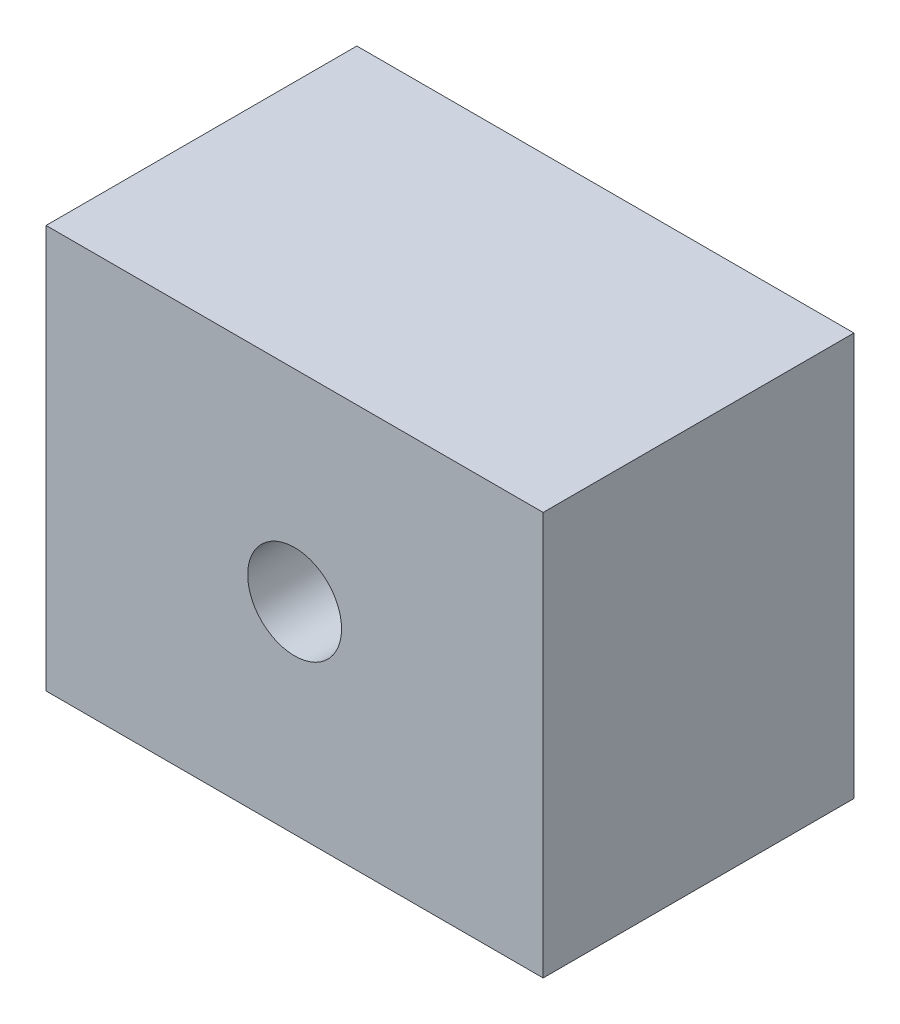
SolidWorks part; units mm, degrees
ref_plane "Front Plane" through (0, 0, 0) normal (0, 0, 1) x (1, 0, 0)
ref_plane "Top Plane" through (0, 0, 0) normal (0, 1, 0) x (1, 0, 0)
ref_plane "Right Plane" through (0, 0, 0) normal (1, 0, 0) x (0, 0, -1)
sketch "Sketch2" plane through (0, 0, 0) normal (0, 0, 1) x (1, 0, 0)
  line L1 (-67.2388, -54.5382) -> (67.2388, -54.5382)
  line L2 (-67.2388, -54.5382) -> (-67.2388, 54.5382)
  line L3 (-67.2388, 54.5382) -> (67.2388, 54.5382)
  line L4 (67.2388, -54.5382) -> (67.2388, 54.5382)
  line L5 (-67.2388, -54.5382) -> (67.2388, 54.5382) construction
  line L6 (-67.2388, 54.5382) -> (67.2388, -54.5382) construction
  point P0 (0, 0)
extrude "Boss-Extrude1" add sketch "Sketch2" along normal blind 84.074
sketch "Sketch3" plane through (0, 0, 84.074) normal (0, 0, 1) x (1, 0, 0)
  circle A0 centre (0, 0) radius 12.7
  dimension "D1" = 25.4
extrude "Cut-Extrude1" cut sketch "Sketch3" against normal blind 127
